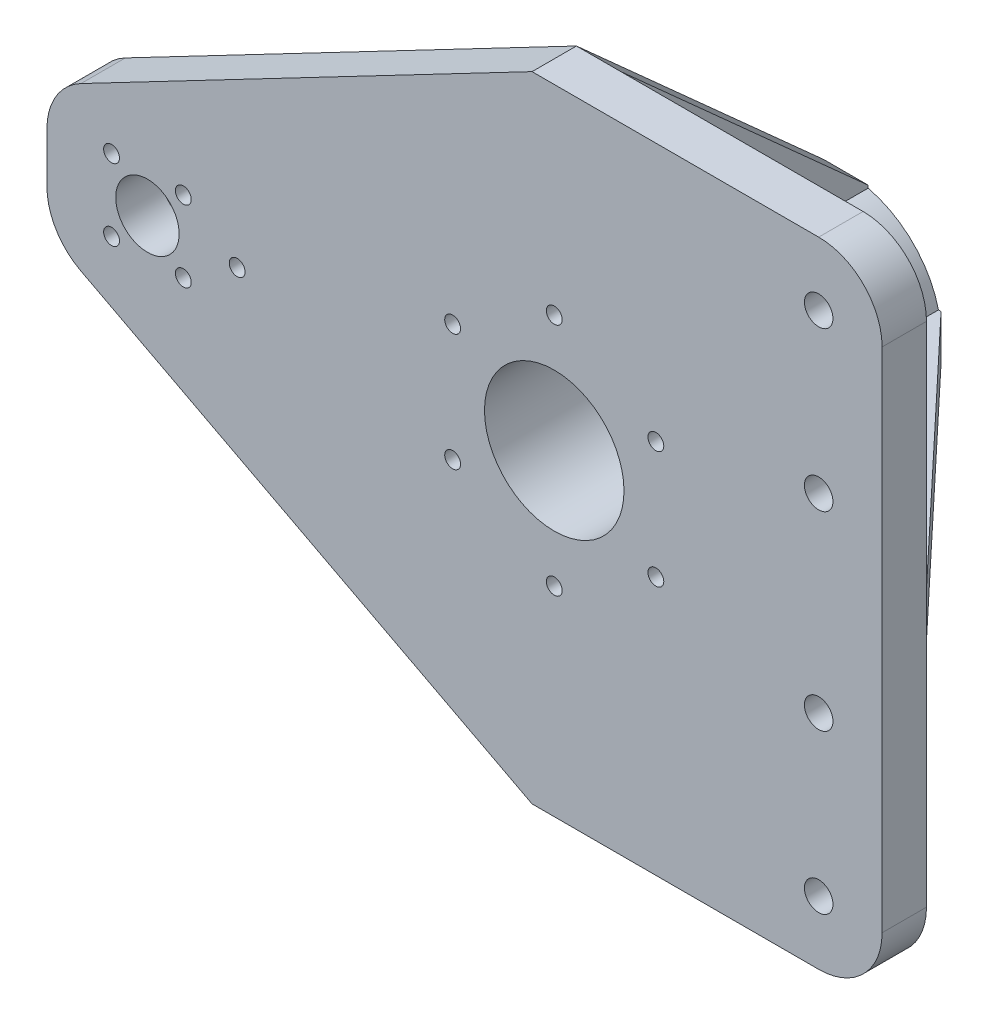
SolidWorks part; units mm, degrees
ref_plane "Front Plane" through (0, 0, 0) normal (0, 0, 1) x (1, 0, 0)
ref_plane "Top Plane" through (0, 0, 0) normal (0, 1, 0) x (1, 0, 0)
ref_plane "Right Plane" through (0, 0, 0) normal (1, 0, 0) x (0, 0, -1)
sketch "Sketch1" plane through (0, 0, 0) normal (0, 0, 1) x (1, 0, 0)
  line L1 (51.7, -50) -> (-80, -50)
  line L2 (51.7, -50) -> (51.7, 50)
  line L3 (51.7, 50) -> (-80, 50)
  line L4 (-80, -50) -> (-80, 50)
  circle A0 centre (0, 0) radius 11
  circle A1 centre (-64.15, 0) radius 5
  dimension "D3" = 22
  dimension "D6" = 10
  dimension "D1" = 100
  dimension "D2" = 50
  dimension "D4" = 80
  dimension "D5" = 51.7
  dimension "D7" = 64.15
extrude "Boss-Extrude1" add sketch "Sketch1" along normal blind 7
sketch "Sketch2" plane through (0, 0, 0) normal (0, 0, -1) x (-1, 0, 0)
  line L0 (-51.7, 50) -> (80, 50) construction
  line L1 (-3.5, -50) -> (3.5, -50)
  line L2 (-3.5, -50) -> (-3.5, -14.586)
  line L3 (-3.5, 50) -> (3.5, 50)
  line L4 (3.5, -50) -> (3.5, -14.586)
  line L5 (-3.5, -50) -> (3.5, 50) construction
  line L6 (-3.5, 50) -> (3.5, -50) construction
  line L7 (-3.5, 14.586) -> (-3.5, 50)
  line L8 (3.5, 14.586) -> (3.5, 50)
  line L9 (-51.7, -50) -> (-51.7, 50) construction
  line L10 (55, 3.5) -> (14.586, 3.5)
  line L11 (55, 3.5) -> (55, -3.5)
  line L12 (55, -3.5) -> (14.586, -3.5)
  line L13 (-51.7, 3.5) -> (-51.7, -3.5)
  line L16 (-14.586, 3.5) -> (-51.7, 3.5)
  line L17 (-14.586, -3.5) -> (-51.7, -3.5)
  circle A0 centre (0, 0) radius 11
  arc A1 (-3.5, 14.586) -> (-14.586, 3.5) centre (0, 0) ccw
  arc A2 (3.5, -14.586) -> (14.586, -3.5) centre (0, 0) ccw
  arc A3 (-14.586, -3.5) -> (-3.5, -14.586) centre (0, 0) ccw
  arc A4 (14.586, 3.5) -> (3.5, 14.586) centre (0, 0) ccw
  dimension "D1" = 30
  dimension "D6" = 22
  dimension "D2" = 7
  dimension "D3" = 7
  dimension "D4" = 3.5
  dimension "D5" = 55
extrude "Boss-Extrude2" add sketch "Sketch2" along normal blind 39
sketch "Sketch3" plane through (3.5, 0, 0) normal (1, 0, 0) x (0, 0, -1)
  line L0 (0, 50) -> (39, 15)
  line L1 (39, 15) -> (39, 50)
  line L2 (39, 50) -> (0, 50)
  line L3 (39, -15) -> (0, -50)
  line L4 (0, -50) -> (39, -50)
  line L5 (39, -50) -> (39, -15)
  dimension "D1" = 15
  dimension "D2" = 15
extrude "Cut-Extrude1" cut sketch "Sketch3" against normal blind 20
sketch "Sketch4" plane through (0, -3.5, 0) normal (0, -1, 0) x (1, 0, 0)
  line L0 (51.7, 0) -> (15, -39)
  line L1 (51.7, -39) -> (14.586, -39) construction
  line L2 (15, -39) -> (51.7, -39)
  line L3 (51.7, -39) -> (51.7, 0) construction
  line L4 (51.7, -39) -> (51.7, 0)
  line L5 (-15, -39) -> (-55, 0)
  line L6 (-14.586, -39) -> (-55, -39) construction
  line L7 (-55, 0) -> (-55, -39)
  line L8 (-55, -39) -> (-15, -39)
  dimension "D1" = 15
  dimension "D2" = 15
extrude "Cut-Extrude2" cut sketch "Sketch4" against normal blind 20
sketch "Sketch5" plane through (0, 0, 0) normal (0, 0, -1) x (-1, 0, 0)
  line L0 (3.5, 50) -> (80, 10)
  line L1 (80, 50) -> (80, -50) construction
  line L2 (80, 10) -> (80, -10)
  line L3 (80, -10) -> (3.5, -50)
  line L4 (3.5, -50) -> (-3.5, -50) construction
  line L5 (3.5, -50) -> (3.5, -14.586) construction
  line L6 (3.5, -50) -> (80, -50)
  line L7 (80, -50) -> (91.7448, -27.538)
  line L8 (91.7448, -27.538) -> (91.7448, 22.5444)
  line L9 (91.7448, 22.5444) -> (80, 50)
  line L10 (80, 50) -> (3.5, 50)
  circle A0 centre (64.15, 0) radius 5 construction
  dimension "D1" = 10
  dimension "D2" = 10
extrude "Cut-Extrude3" cut sketch "Sketch5" against normal blind 10
fillet "Fillet1" radius 10 4 edges at (51.7, 50, 3.5) (51.7, -50, 3.5) (-80, -10, 3.5) (-80, 10, 3.5)
sketch "Sketch6" plane through (0, 0, 7) normal (0, 0, 1) x (1, 0, 0)
  line L1 (-69.8069, 5.6569) -> (-58.4931, 5.6569) construction
  line L2 (-69.8069, 5.6569) -> (-69.8069, -5.6569) construction
  line L3 (-69.8069, -5.6569) -> (-58.4931, -5.6569) construction
  line L4 (-58.4931, 5.6569) -> (-58.4931, -5.6569) construction
  line L5 (-69.8069, 5.6569) -> (-58.4931, -5.6569) construction
  line L6 (-69.8069, -5.6569) -> (-58.4931, 5.6569) construction
  circle A0 centre (-69.8069, 5.6569) radius 1.25
  circle A1 centre (-58.4931, 5.6569) radius 1.25
  circle A2 centre (-69.8069, -5.6569) radius 1.25
  circle A3 centre (-58.4931, -5.6569) radius 1.25
  point P0 (-64.15, 0)
  dimension "D3" = 2.5
  dimension "D1" = 16
extrude "Cut-Extrude4" cut sketch "Sketch6" against normal blind 10
sketch "Sketch7" plane through (0, 0, 0) normal (0, 0, -1) x (-1, 0, 0)
  line L0 (-51.7, 3.5) -> (-51.7, 40) construction
  line L1 (-41.7, 50) -> (-3.5, 50) construction
  line L2 (-3.5, -50) -> (-41.7, -50) construction
  circle A0 centre (-41.7, 40) radius 2.25
  circle A1 centre (-41.7, 15) radius 2.25
  circle A2 centre (-41.7, -15) radius 2.25
  circle A3 centre (-41.7, -40) radius 2.25
  dimension "D1" = 4.5
  dimension "D2" = 10
  dimension "D3" = 10
  dimension "D4" = 10
  dimension "D5" = 25
  dimension "D6" = 25
extrude "Cut-Extrude5" cut sketch "Sketch7" against normal blind 15
sketch "Sketch8" plane through (0, 0, 7) normal (0, 0, 1) x (1, 0, 0)
  circle A0 centre (0, 18.5) radius 1.25
  circle A1 centre (16.0215, 9.25) radius 1.25
  circle A2 centre (16.0215, -9.25) radius 1.25
  circle A3 centre (0, -18.5) radius 1.25
  circle A4 centre (-16.0215, -9.25) radius 1.25
  circle A5 centre (-16.0215, 9.25) radius 1.25
  circle A6 centre (-50, 0) radius 1.25
  point P16 (0, 0)
  dimension "D1" = 18.5
  dimension "D2" = 2.5
  dimension "D4" = 50
  dimension "D3" = 6
extrude "Cut-Extrude6" cut sketch "Sketch8" against normal blind 20
